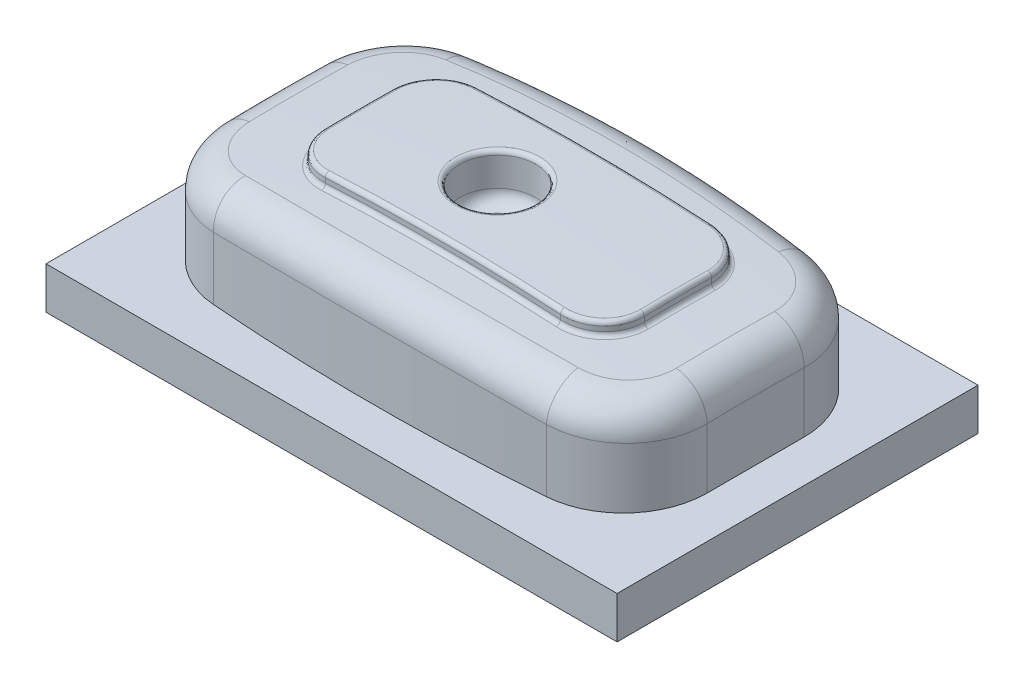
SolidWorks part; units mm, degrees
ref_plane "정면" through (0, 0, 0) normal (0, 0, 1) x (1, 0, 0)
ref_plane "윗면" through (0, 0, 0) normal (0, 1, 0) x (1, 0, 0)
ref_plane "우측면" through (0, 0, 0) normal (1, 0, 0) x (0, 0, -1)
sketch "스케치1" plane through (0, 0, 0) normal (0, 1, 0) x (1, 0, 0)
  line L5 (-74.6, 43) -> (61.5, 43)
  line L6 (-74.6, 43) -> (-74.6, -43)
  line L7 (-74.6, -43) -> (61.5, -43)
  line L8 (61.5, 43) -> (61.5, -43)
  dimension "D1" = 74.6
  dimension "D2" = 61.5
  dimension "D3" = 86
  dimension "D4" = 43
extrude "보스-돌출2" add sketch "스케치1" along normal blind 10
sketch "스케치3" plane through (0, 10, 0) normal (0, 1, 0) x (1, 0, 0)
  line L4 (0, 74.0647) -> (0, -68.2345) construction
  line L5 (-64.6, 11.5324) -> (-64.6, -11.5324)
  line L7 (51.5, -11.5324) -> (51.5, 11.5324)
  line L9 (-74.6, 43) -> (-74.6, -43) construction
  line L10 (61.5, -43) -> (61.5, 43) construction
  line L11 (-93.8881, 0) -> (95.5335, 0) construction
  arc A6 (33.0854, 31.4695) -> (-46.1854, 31.4695) centre (-6.55, -466.9571) ccw
  arc A7 (33.0854, -31.4695) -> (-46.1854, -31.4695) centre (-6.55, 466.9571) cw
  arc A8 (51.5, 11.5324) -> (33.0854, 31.4695) centre (31.5, 11.5324) ccw
  arc A9 (51.5, -11.5324) -> (33.0854, -31.4695) centre (31.5, -11.5324) cw
  arc A10 (-46.1854, -31.4695) -> (-64.6, -11.5324) centre (-44.6, -11.5324) cw
  arc A11 (-64.6, 11.5324) -> (-46.1854, 31.4695) centre (-44.6, 11.5324) cw
  point P14 (0, -33)
  point P15 (0, 0)
  point P17 (0, 0)
  point P18 (51.5, -35.58)
  point P20 (0, 33)
  point P22 (51.5, 29.6617)
  point P25 (51.5, -29.6617)
  point P28 (-64.6, -29.6617)
  point P31 (-64.6, 29.6617)
  dimension "D5" = 20
  dimension "D3" = 1000
  dimension "D4" = 33
  dimension "D1" = 10
  dimension "D2" = 10
extrude "보스-돌출3" add sketch "스케치3" along normal blind 60
sketch "스케치6" plane through (0, 0, 0) normal (0, 0, 1) x (1, 0, 0)
  line L0 (-64.6, 70) -> (-64.6, 10) construction
  line L1 (51.5, 70) -> (51.5, 10) construction
  line L2 (-29.3428, 35) -> (4.5465, 35) construction
  line L3 (-10, 56.1433) -> (-10, 18.3552) construction
  arc A0 (-64.6, 31.6188) -> (51.5, 31.6188) centre (-6.55, -465) cw construction
  dimension "D1" = 500
  dimension "D2" = 10
  dimension "D3" = 35
sketch "스케치7" plane through (0, 0, 0) normal (1, 0, 0) x (0, 0, -1)
  line L0 (-33.0429, 70) -> (-33.0429, 10) construction
  line L1 (33.0429, 10) -> (33.0429, 70) construction
  arc A0 (-33.0429, 33.907) -> (33.0429, 33.907) centre (0, -465) cw
  point P3 (0, 0)
  dimension "D1" = 500
sketch "스케치8" plane through (0, 0, 0) normal (0, 0, 1) x (1, 0, 0)
  line L0 (-64.6, 31.6188) -> (-64.6, 80)
  line L1 (-64.6, 80) -> (51.5, 80)
  line L2 (51.5, 80) -> (51.5, 31.6188)
  line L4 (33.0854, 70) -> (-46.1854, 70) construction
  arc A0 (-64.6, 31.6188) -> (51.5, 31.6188) centre (-6.55, -465) cw
  dimension "D1" = 500
  dimension "D2" = 10
sweep "컷-스윕1" cut profiles "스케치8" path "스케치7"
sketch "스케치9" plane through (0, 10, 0) normal (0, 1, 0) x (1, 0, 0)
  line L1 (-33, 18) -> (23, 18)
  line L2 (-43, 8) -> (-43, -8)
  line L3 (-33, -18) -> (23, -18)
  line L4 (33, 8) -> (33, -8)
  arc A0 (23, 18) -> (33, 8) centre (23, 8) cw
  arc A1 (33, -8) -> (23, -18) centre (23, -8) cw
  arc A2 (-33, -18) -> (-43, -8) centre (-33, -8) cw
  arc A3 (-43, 8) -> (-33, 18) centre (-33, 8) cw
  dimension "D5" = 10
  dimension "D1" = 33
  dimension "D2" = 43
  dimension "D3" = 18
  dimension "D4" = 36
extrude "보스-돌출5" add sketch "스케치9" along normal offset from surface (26.8085 mm away) 3
ref_plane "평면1" through (0, 27, 0) normal (0, -1, 0) x (-1, 0, 0)
sketch "스케치11" plane through (0, 27, 0) normal (0, -1, 0) x (-1, 0, 0)
  line L0 (29.3428, 0) -> (-4.5465, 0) construction
  circle A0 centre (10, 0) radius 9
  dimension "D1" = 18
  dimension "D2" = 10
extrude "컷-돌출2" cut sketch "스케치11" against normal through all
fillet "필렛1" radius 8 8 edges at (51.5, 31.6188, 0) (45.2044, 31.629, -26.0991) (-60.2436, 31.5293, -23.9935) (-64.6, 31.6188, 0) (-58.3044, 31.629, 26.0991) (47.1436, 31.5293, 23.9935)
fillet "필렛2" radius 1 17 edges at (-40.8151, 33.6213, 14.2389) (-43, 33.6696, 0) (-39.251, 33.6791, -15.8055) (-4.9976, 34.6735, -18) (30.8166, 33.3985, -14.2371) (33, 33.4333, 0) (29.2524, 33.4661, 15.8043) (30.8165, 36.4081, 14.2372) (33, 36.4427, 0) (29.2523, 36.4752, -15.8044) (-4.9976, 37.6754, -18) (-40.815, 36.6295, -14.239) (-43, 36.6776, 0) (-39.2509, 36.687, 15.8055) (-5.2666, 37.9401, 7.6547) (-4.9976, 34.6735, 18) (-4.9976, 37.6754, 18)
fillet "필렛3" radius 3 1 edges at (-10, 27, -9)
